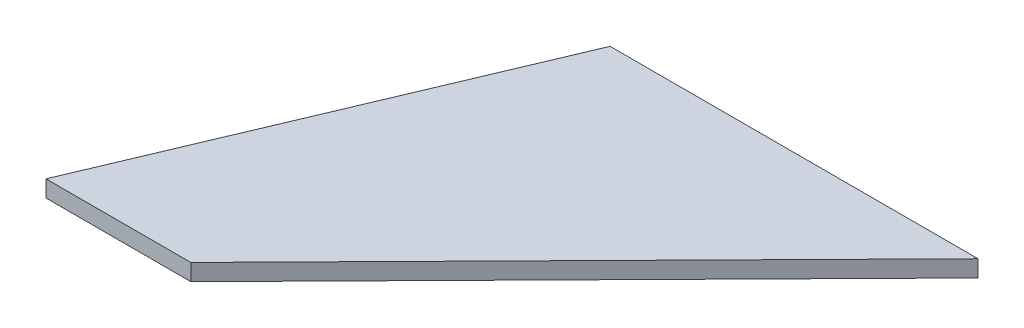
SolidWorks part; units mm, degrees
ref_plane "Front Plane" through (0, 0, 0) normal (0, 0, 1) x (1, 0, 0)
ref_plane "Top Plane" through (0, 0, 0) normal (0, 1, 0) x (1, 0, 0)
ref_plane "Right Plane" through (0, 0, 0) normal (1, 0, 0) x (0, 0, -1)
sketch "Sketch1" plane through (0, 0, 0) normal (0, 1, 0) x (1, 0, 0)
  line L1 (0, 0) -> (263.3435, 0)
  line L2 (0, 0) -> (0, 204.1914)
  line L3 (0, 204.1914) -> (263.3435, 204.1914)
  line L4 (263.3435, 0) -> (263.3435, 204.1914)
  line L5 (0, 0) -> (263.3435, 204.1914) construction
  line L6 (0, 204.1914) -> (263.3435, 0) construction
  point P4 (131.6717, 102.0957)
  dimension "D1" = 263.3435
  dimension "D2" = 204.1914
extrude "Boss-Extrude1" add sketch "Sketch1" along normal blind 4.6
sketch "Sketch2" plane through (0, 0, 0) normal (0, -1, 0) x (1, 0, 0)
  line L8 (182.5435, -204.1914) -> (80.9435, -204.1914)
  line L9 (80.9435, -204.1914) -> (80.9435, -208.7124)
  line L10 (80.9435, -208.7124) -> (182.5435, -208.7124)
  line L11 (182.5435, -208.7124) -> (182.5435, -204.1914)
  line L12 (34.7435, -94.6106) -> (74.7435, -94.6106)
  line L13 (34.7435, -55.0027) -> (34.7435, -94.6106)
  line L14 (34.7435, -55.0027) -> (74.7435, -55.0027)
  line L15 (74.7435, -55.0027) -> (74.7435, -94.6106)
  line L16 (182.5435, -204.1914) -> (74.7435, -94.6106)
  line L17 (80.9435, -204.1914) -> (34.7435, -94.6106)
  line M6 (0, -204.1914) -> (263.3435, -204.1914)
extrude "Cut-Extrude1" cut sketch "Sketch2" against normal through all flip side to cut contours L17 L16 L12 M6 region at (98.8264, 0, -157.3461)
equation "\"MDF\"= 4.8mm"
equation "\"Foamcore\"= 4.6mm"
equation "\"GMaterial\"= \"MDF\""
equation "\"PCB\" = 1.6mm"
equation "\"BaseWidth\" = 10in"
equation "\"SkidLength\" = 1in"
equation "\"SkidClearance\" = 0.4in"
equation "\"MotorMountLength\" = 2in"
equation "\"MotorMountWidth\" = \"GMaterial\""
equation "\"MotorMountHeight\" = 2.25in"
equation "\"UnoStackWidth\" = 77.4mm"
equation "\"UnoStackLength\" = 79.8mm"
equation "\"UnoStackHeight\" = 34.2mm"
equation "\"TallHexRiserHeight\" = 22.2mm"
equation "\"PingPongBallSize\" = 40mm"
equation "\"BarrelLength\" = 9in"
equation "\"BarrelSize\" = \"PingPongBallSize\""
equation "\"PlatformLength\" = 4in"
equation "\"PlatformWidth\" = 6in"
equation "\"WheelDiameter\"=2.99213"
equation "\"ServoMountHeight\"=2.49223"
equation "\"ServoGearHeight\" = 0.95330261in"
equation "\"ServoMountLength\"= 1.53774"
equation "\"PivotHoleRadius\"= 0.616358"
equation "\"PlatformMountHeight\" = 3.19"
equation "\"TensionOffSet\"= .3mm"
equation "\"MotorMountWedge\"=0.333333"
equation "\"LaserCutterOffset\"= .3mm"
equation "\"BumperWidth\"=11"
equation "\"PitcherWheelCompression\" = 2.5mm"
equation "\"BarrelToHopperDistance\" = 0.5405in"
equation "\"PitchingWheelWidth\" = 26.2mm"
equation "\"PitchingWheelDiameter\" = 65.5mm"
equation "\"PitchingWheelMountOffset\" = 8.4mm"
equation "\"PitchingWheelInnerDiameter\" = 45.5mm"
equation "\"PitchingWheelBoltShoulder\" = 4.5mm"
equation "\"BrassCouplingLength\" = 18mm"
equation "\"PitchingMotorHeight\" = 57.0mm"
equation "\"PitchingMotorShaftTopHeight\" = \"PitchingMotorHeight\" - 44.1mm"
equation "\"PitchingMotorBodyHeight\" = 38mm"
equation "\"PitchingMotorTopShoulderHeight\" = 40.6mm - \"PitchingMotorBodyHeight\" "
equation "\"PitchingMotorBottomShoulderHeight\" = 40.2mm - \"PitchingMotorBodyHeight\""
equation "\"PitchingMotorBottomShaftHeight\" = \"PitchingMotorHeight\" - \"PitchingMotorShaftTopHeight\" - \"PitchingMotorTopShoulderHeight\" - \"PitchingMotorBodyHeight\" - \"PitchingMotorBottomShoulderHeight\""
equation "\"PitchingMotorShaftDiameter\" = 2.2mm"
equation "\"PitchingMotorBodyDiameter\" = 27.4mm"
equation "\"PitchingMotorTopShoulderDiameter\" = 9.8mm"
equation "\"PitchingMotorBottomShoulderDiameter\" = 9.8mm"
equation "\"BrassCouplingHexSize\" = 12mm"
equation "\"BrassCouplingBoreSize\" = 3.17mm"
equation "\"PitchingMotorMountingHoleDistance\" = 16mm"
equation "\"Acrylic\" = 4.4mm"
equation "\"PitchingMotorDistance\" = \"PitchingWheelDiameter\" + \"PingPongBallSize\" - \"PitcherWheelCompression\"*2"
equation "\"PitchingMotorPlatformOffset\"=1"
equation "\"ServoPlatformOffset\"=1.64173"
equation "\"BallBearingDiameter\" = 22mm"
equation "\"BallBearingWidth\" = 9mm"
equation "\"BallBearingHexShoulder\" = 9mm - 5.9mm"
equation "\"BallBearingHexSize\" = .36in"
equation "\"PlatformMountFootLength\"=0.857143"
equation "\"WheelWidth\"= 26mm"
equation "\"ServoMountReductionBackHeight\"=2.25"
equation "\"PlatformBottomWidthThird\" =  0.857143in"
equation "\"PlatformMountBackReductionHeight\"= 2.5in"
equation "\"PlatformMountBackReductionWidth\"= 3/7in"
equation "\"PlatformMountFrontReductionWidth\" =  1.46226in"
equation "\"PlatformMountFrontReductionHeight\" = 2.5in"
equation "\"HopperLongWallLength\" = 8.646in"
equation "\"HopperShortWallLength\" = 0.9571in"
equation "\"HopperHeight\" = 3.50in - \"Foamcore\""
equation "\"HoperLongSlantLength\" = 7.064in"
equation "\"HopperBottomTemplateWidth\" = 8.03903165in"
equation "\"HopperBottomTemplateLength\" = 10.367854in"
equation "\"D1@Sketch1\"=\"HopperBottomTemplateLength\""
equation "\"D2@Sketch1\"=\"HopperBottomTemplateWidth\""
equation "\"D1@Boss-Extrude1\"=\"Foamcore\""
